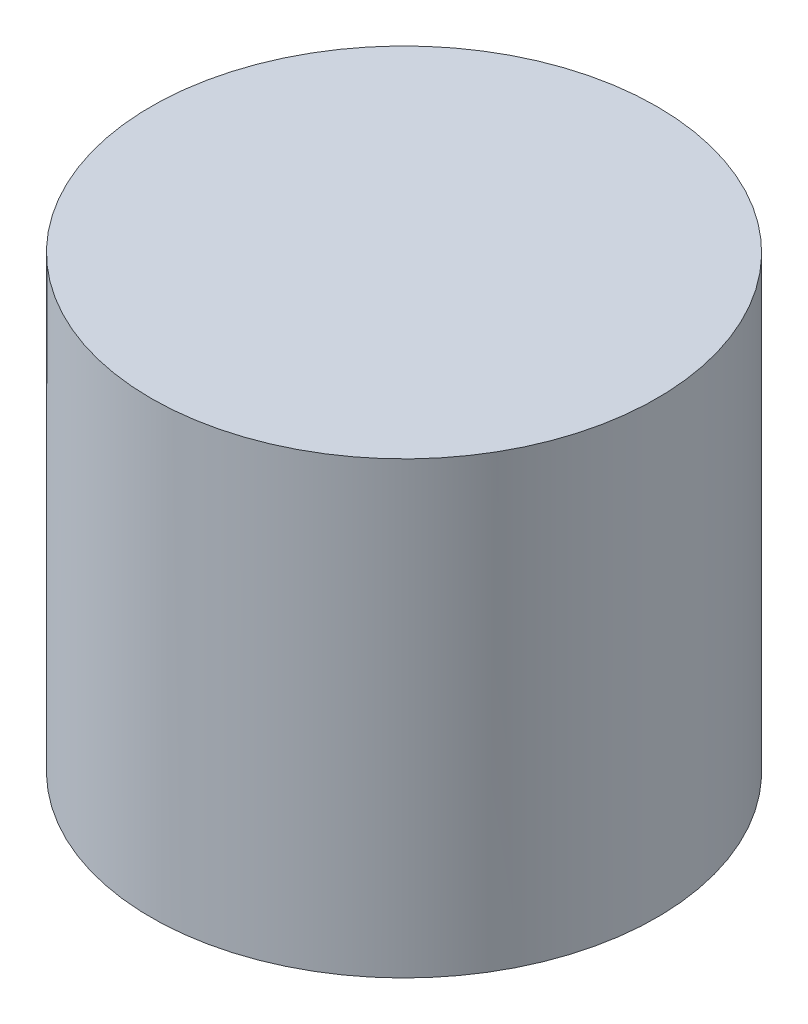
SolidWorks part; units mm, degrees
ref_plane "Alzado" through (0, 0, 0) normal (0, 0, 1) x (1, 0, 0)
ref_plane "Planta" through (0, 0, 0) normal (0, 1, 0) x (1, 0, 0)
ref_plane "Vista lateral" through (0, 0, 0) normal (1, 0, 0) x (0, 0, -1)
sketch "Sketch1" plane through (0, 0, 0) normal (0, 1, 0) x (1, 0, 0)
  circle A0 centre (0, 0) radius 22.5
  dimension "D1" = 45
extrude "Boss-Extrude1" add sketch "Sketch1" along normal blind 3
sketch "Sketch2" plane through (0, 0, 0) normal (0, -1, 0) x (-1, 0, 0)
  circle A0 centre (0, 0) radius 18
  circle A1 centre (0, 0) radius 22.5
  dimension "D1" = 36
  dimension "D2" = 45
extrude "Boss-Extrude2" add sketch "Sketch2" along normal blind 37
fillet "Fillet1" radius 5 1 edges at (0, -37, -18)
sketch "Sketch3" plane through (0, 3, 0) normal (0, 1, 0) x (1, 0, 0)
  circle A0 centre (0, 0) radius 18
  circle A1 centre (0, 0) radius 17.1
  circle A2 centre (0, 0) radius 17 construction
  dimension "D1" = 36
  dimension "D3" = 0.1
extrude "Boss-Extrude3" add sketch "Sketch3" against normal blind 6
